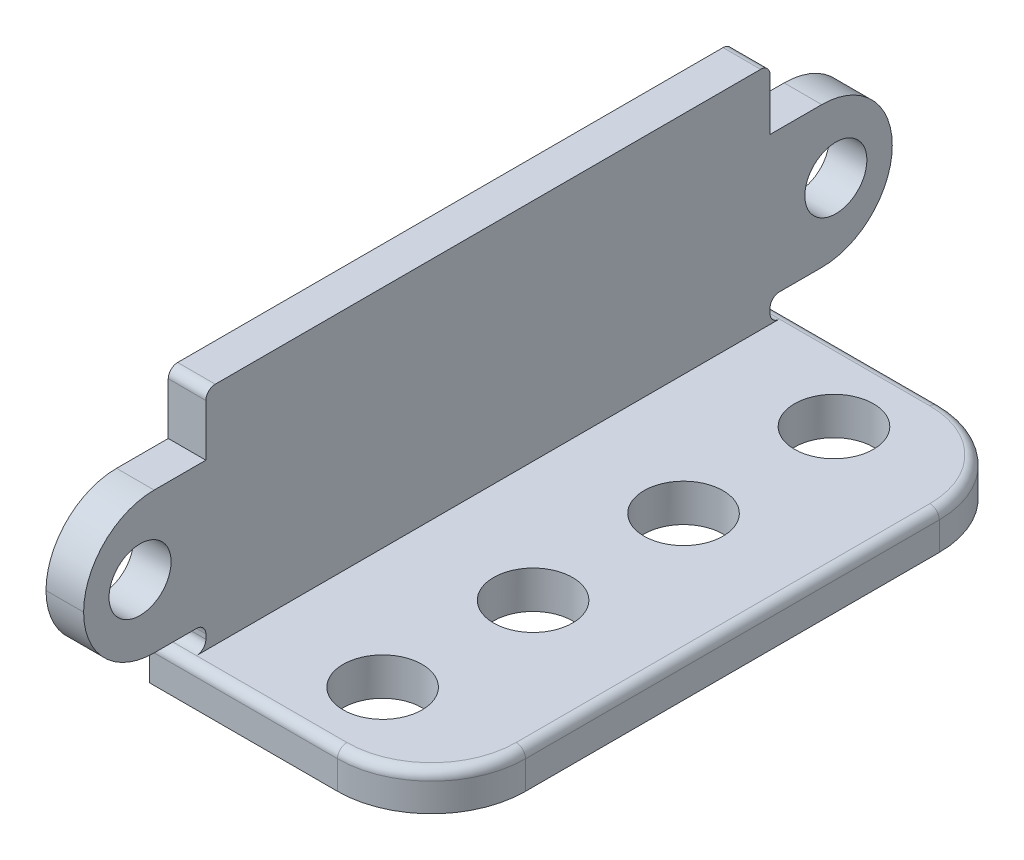
SolidWorks part; units mm, degrees
ref_plane "前基準面" through (0, 0, 0) normal (0, 0, 1) x (1, 0, 0)
ref_plane "上基準面" through (0, 0, 0) normal (0, 1, 0) x (1, 0, 0)
ref_plane "右基準面" through (0, 0, 0) normal (1, 0, 0) x (0, 0, -1)
sketch "草圖1" plane through (0, 0, 0) normal (1, 0, 0) x (0, 0, -1)
  line L1 (-21.5, 3.75) -> (21.5, 3.75)
  line L2 (-21.5, 3.75) -> (-21.5, -3.75)
  line L3 (-21.5, -3.75) -> (21.5, -3.75)
  line L4 (21.5, 3.75) -> (21.5, -3.75)
  line L5 (-21.5, 3.75) -> (21.5, -3.75) construction
  line L6 (-21.5, -3.75) -> (21.5, 3.75) construction
  point P0 (0, 0)
  dimension "D1" = 43
  dimension "D2" = 7.5
extrude "填料-伸長1" add sketch "草圖1" along normal blind 2
sketch "草圖2" plane through (2, 0, 0) normal (1, 0, 0) x (0, 0, -1)
  circle A2 centre (-18.5, 0) radius 1.65
  circle A3 centre (18.5, 0) radius 1.65
  dimension "D1" = 37
  dimension "D2" = 18.5
  dimension "D3" = 3.3
  dimension "D4" = 3.3
extrude "除料-伸長2" cut sketch "草圖2" against normal blind 11.5
fillet "圓角1" radius 3.75 4 edges at (1, -3.75, -21.5) (1, 3.75, -21.5) (1, -3.75, 21.5) (1, 3.75, 21.5)
sketch "草圖3" plane through (0, 0, 0) normal (-1, 0, 0) x (0, 0, 1)
  line L1 (15, -7) -> (-15, -7)
  line L2 (15, -7) -> (15, 7)
  line L3 (15, 7) -> (-15, 7)
  line L4 (-15, -7) -> (-15, 7)
  line L5 (15, -7) -> (-15, 7) construction
  line L6 (15, 7) -> (-15, -7) construction
  point P0 (0, 0)
  dimension "D1" = 14
  dimension "D2" = 30
extrude "填料-伸長3" add sketch "草圖3" against normal up to vertex (2 mm away) up to point (2, 3.75, 17.75)
sketch "草圖4" plane through (0, -7, 0) normal (0, 1, 0) x (1, 0, 0)
  line L1 (0, 16) -> (15, 16)
  line L2 (0, 16) -> (0, -16)
  line L3 (0, -16) -> (15, -16)
  line L4 (15, 16) -> (15, -16)
  line L5 (0, 15) -> (0, -15) construction
  line L6 (2, -17.75) -> (0, -17.75) construction
  dimension "D1" = 15
  dimension "D2" = 32
  dimension "D3" = 16
extrude "填料-伸長4" add sketch "草圖4" along normal blind 2
sketch "草圖5" plane through (0, -5, 0) normal (0, 1, 0) x (-1, 0, 0)
  line L2 (0, 16) -> (-15, 16) construction
  line L4 (-2, -15) -> (-2, 15) construction
  circle A0 centre (-8.4, 12) radius 2.1
  circle A1 centre (-8.4, 4) radius 2.1
  circle A2 centre (-8.4, -4) radius 2.1
  circle A3 centre (-8.4, -12) radius 2.1
  point P2 (-7.9, 13.5829)
  point P4 (-7.8763, 12)
  dimension "D1" = 4
  dimension "D3" = 4.2
  dimension "D2" = 6.4
  dimension "D4" = 4
extrude "除料-伸長3" cut sketch "草圖5" against normal blind 13
fillet "圓角3" radius 5 2 edges at (15, -6, -16) (15, -6, 16)
fillet "圓角5" radius 0.5 4 edges at (1, -5, -15) (1, -3.75, -15) (1, -3.75, 15) (1, -5, 15)
fillet "圓角6" radius 0.5 5 edges at (5, -5, 16) (13.5355, -5, 14.5355) (15, -5, 0) (13.5355, -5, -14.5355) (5, -5, -16)
fillet "圓角7" radius 0.5 2 edges at (1, 7, 15) (1, 7, -15)
